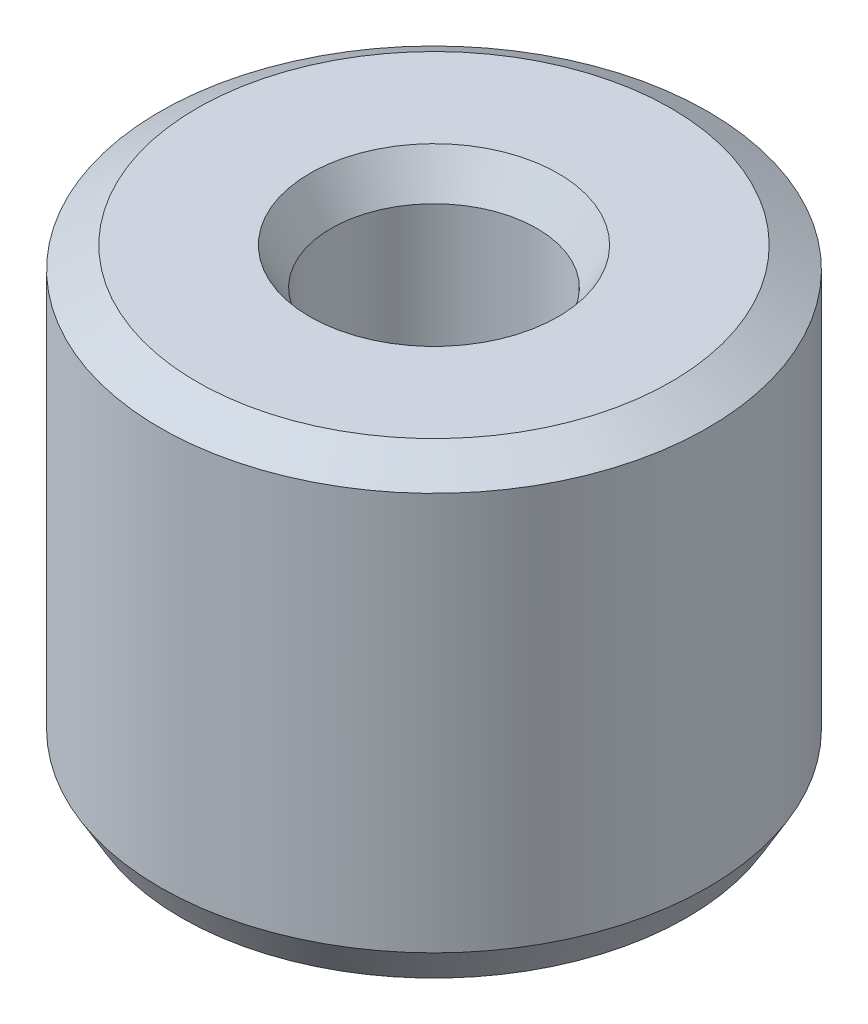
SolidWorks part; units mm, degrees
ref_plane "Front Plane" through (0, 0, 0) normal (0, 0, 1) x (1, 0, 0)
ref_plane "Top Plane" through (0, 0, 0) normal (0, 1, 0) x (1, 0, 0)
ref_plane "Right Plane" through (0, 0, 0) normal (1, 0, 0) x (0, 0, -1)
sketch "Sketch1" plane through (0, 0, 0) normal (0, 1, 0) x (1, 0, 0)
  circle A0 centre (0, 0) radius 22.5
  dimension "SLEEVE_OD" = 45
extrude "Boss-Extrude1" add sketch "Sketch1" along normal blind 37.4681
sketch "Sketch2" plane through (0, 0, 0) normal (0, 1, 0) x (1, 0, 0)
  circle A0 centre (0, 0) radius 8.4477
  dimension "BORE_D" = 16.8953
extrude "Cut-Extrude1" cut sketch "Sketch2" along normal through all
chamfer "Chamfer1" distance 1.7515 angle 60 4 edges at (0, 37.4681, 8.4477) (0, 0, 8.4477) (0, 0, 22.5) (0, 37.4681, 22.5) first distance on face at (0, 37.4681, 8.4477) first distance on face at (0, 0, 8.4477) first distance on face at (0, 37.4681, 22.5)
